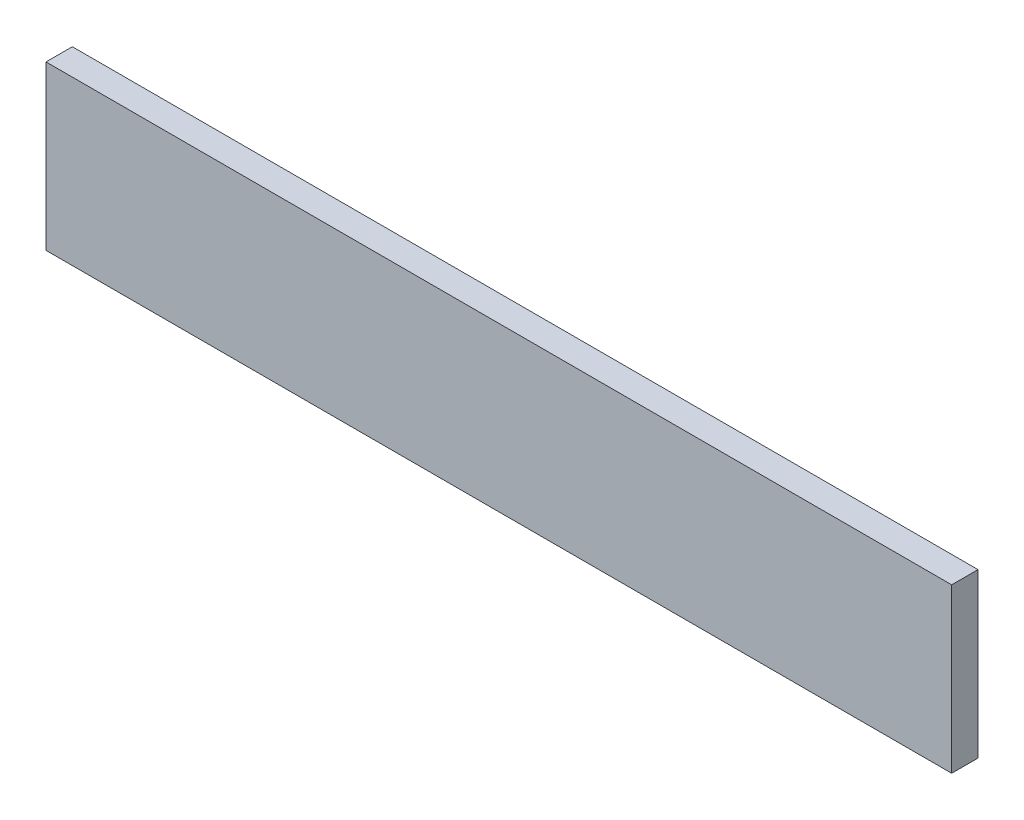
SolidWorks part; units mm, degrees
ref_plane "Front Plane" through (0, 0, 0) normal (0, 0, 1) x (1, 0, 0)
ref_plane "Top Plane" through (0, 0, 0) normal (0, 1, 0) x (1, 0, 0)
ref_plane "Right Plane" through (0, 0, 0) normal (1, 0, 0) x (0, 0, -1)
sketch "Sketch1" plane through (0, 0, 0) normal (0, 0, 1) x (1, 0, 0)
  line L1 (0, 0) -> (860, 0)
  line L2 (0, 0) -> (0, 155)
  line L3 (0, 155) -> (860, 155)
  line L4 (860, 0) -> (860, 155)
  dimension "D1" = 860
  dimension "D2" = 155
extrude "Boss-Extrude1" add sketch "Sketch1" along normal blind 25
ref_axis "Axis1" through (0, 77.5, 25) along (1, 0, 0)
sketch "Sketch2" plane through (0, 0, 25) normal (0, 0, 1) x (1, 0, 0)
  line L0 (0, 77.5) -> (860, 77.5) construction
  line L1 (0, 155) -> (0, 0) construction
  line L2 (860, 0) -> (860, 155) construction
  point P0 (10, 77.5)
  point P5 (850, 77.5)
  line B0 (666.3249, 79.116) -> (198.6756, 85.8846)
  line B1 (41.0836, 98.6002) -> (177.6737, 140.36)
  line B2 (666.3249, 135.211) -> (202.6475, 128.4999)
  line B3 (193.5314, 75.958) -> (661.1807, 69.1894)
  line B4 (818.7727, 56.4739) -> (682.1826, 14.7141)
  line B5 (193.5314, 19.8631) -> (657.2088, 26.5742)
  arc B6 (672.6633, 84.3234) -> (674.734, 107.1635) centre (547.734, 107.1635) ccw
  arc B7 (666.3249, 79.116) -> (672.6633, 84.3234) centre (666.4168, 85.4654) ccw
  arc B8 (198.6756, 85.8846) -> (159.9487, 61.3189) centre (198.8633, 42.7802) ccw
  arc B9 (158.6394, 60.4167) -> (159.9487, 61.3189) centre (158.5144, 61.9993) ccw
  arc B10 (113.7859, 64.5429) -> (158.6394, 60.4167) centre (148.1945, 192.7274) ccw
  arc B11 (113.7859, 64.5429) -> (79.1275, 68.6337) centre (81.9932, -55.9521) ccw
  arc B12 (79.1275, 68.6337) -> (73.3161, 64.4835) centre (79.2735, 62.2853) ccw
  arc B13 (41.0836, 98.6002) -> (73.3161, 64.4835) centre (48.7419, 73.551) ccw
  circle B14 centre (53.0484, 90.3059) radius 4.7625
  circle B15 centre (75.1038, 97.0489) radius 4.7625
  circle B16 centre (97.1593, 103.792) radius 4.7625
  circle B17 centre (119.2147, 110.535) radius 4.7625
  circle B18 centre (141.2702, 117.278) radius 4.7625
  circle B19 centre (163.3256, 124.0211) radius 4.7625
  arc B20 (190.3517, 135.6135) -> (177.6737, 140.36) centre (180.9227, 129.733) ccw
  arc B21 (190.3517, 135.6135) -> (202.6475, 128.4999) centre (203.5356, 144.2183) ccw
  arc B22 (672.6633, 130.0036) -> (666.3249, 135.211) centre (666.4168, 128.8616) ccw
  arc B23 (674.734, 107.1635) -> (672.6633, 130.0036) centre (547.734, 107.1635) ccw
  arc B24 (187.193, 70.7507) -> (185.1223, 47.9105) centre (312.1223, 47.9105) ccw
  arc B25 (193.5314, 75.958) -> (187.193, 70.7507) centre (193.4395, 69.6087) ccw
  arc B26 (661.1807, 69.1894) -> (699.9076, 93.7552) centre (660.993, 112.2938) ccw
  arc B27 (701.2169, 94.6573) -> (699.9076, 93.7552) centre (701.3419, 93.0747) ccw
  arc B28 (746.0704, 90.5311) -> (701.2169, 94.6573) centre (711.6618, -37.6534) ccw
  arc B29 (746.0704, 90.5311) -> (780.7288, 86.4404) centre (777.8631, 211.0262) ccw
  arc B30 (780.7288, 86.4404) -> (786.5402, 90.5905) centre (780.5828, 92.7887) ccw
  arc B31 (818.7727, 56.4739) -> (786.5402, 90.5905) centre (811.1144, 81.5231) ccw
  circle B32 centre (806.9521, 64.6947) radius 4.7625
  circle B33 centre (784.8967, 57.9517) radius 4.7625
  circle B34 centre (762.8412, 51.2086) radius 4.7625
  circle B35 centre (740.7858, 44.4656) radius 4.7625
  circle B36 centre (718.7303, 37.7226) radius 4.7625
  circle B37 centre (696.6749, 30.9796) radius 4.7625
  arc B38 (669.5045, 19.4605) -> (682.1826, 14.7141) centre (678.9336, 25.341) ccw
  arc B39 (669.5045, 19.4605) -> (657.2088, 26.5742) centre (656.3206, 10.8558) ccw
  arc B40 (187.193, 25.0704) -> (193.5314, 19.8631) centre (193.4395, 26.2124) ccw
  arc B41 (185.1223, 47.9105) -> (187.193, 25.0704) centre (312.1223, 47.9105) ccw
  dimension "D1" = 10
  dimension "D2" = 10
sketch_block_instance "Block3-1"
sketch_block "Block3" parameters "D1"=5, "D2"=10
ref_axis "Axis2" through (430, 155, 0) along (0, -0.9872, 0.1592)
ref_axis "Axis4" through (10, 77.5, 25) along (0, 0, -1)
ref_axis "Axis5" through (850, 77.5, 25) along (0, 0, -1)
